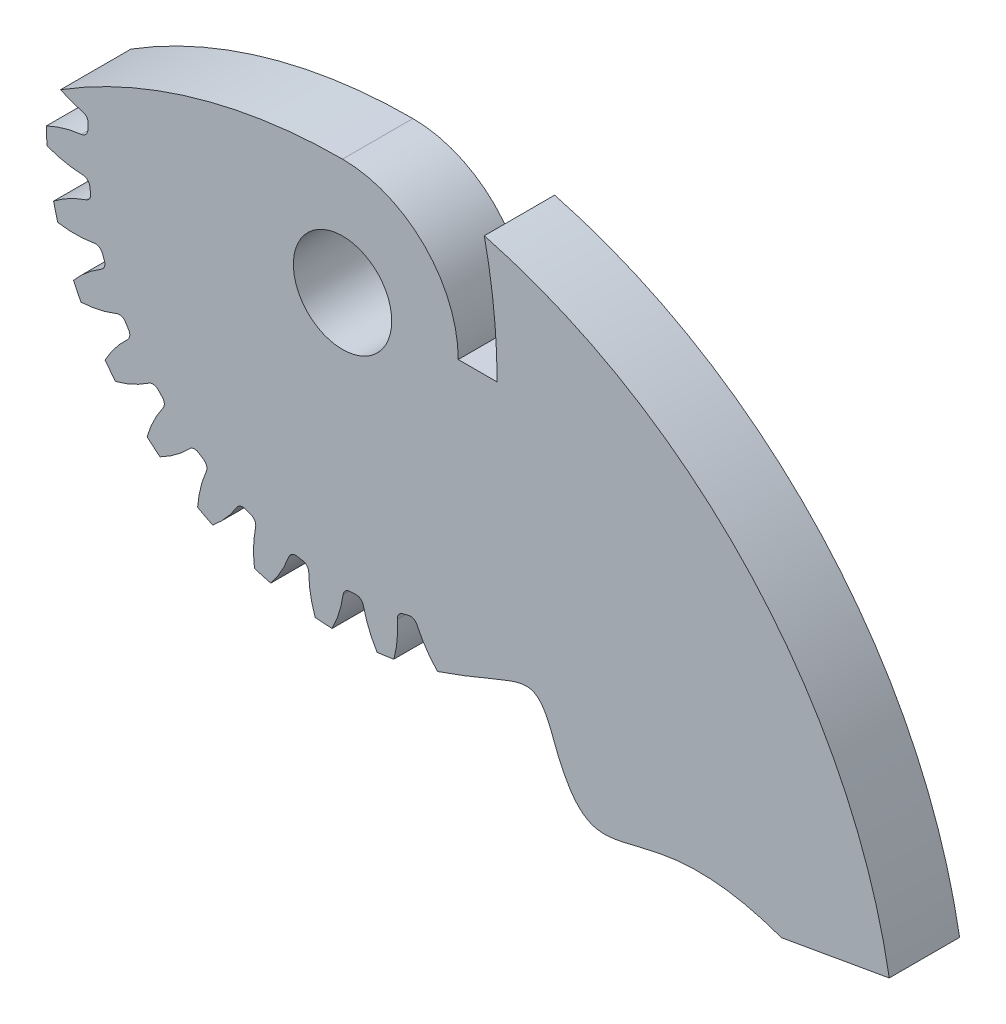
SolidWorks part; units mm, degrees
material "ABS"
ref_plane "Front" through (0, 0, 0) normal (0, 0, 1) x (1, 0, 0)
ref_plane "Top" through (0, 0, 0) normal (0, 1, 0) x (1, 0, 0)
ref_plane "Right" through (0, 0, 0) normal (1, 0, 0) x (0, 0, -1)
sketch "Sketch3" plane through (0, 0, 0) normal (0, 0, 1) x (1, 0, 0)
  circle A0 centre (0, 0) radius 40.64
  dimension "od" = 81.28
extrude "gearBody" add sketch "Sketch3" along normal blind 9.652
sketch "Sketch2" plane through (0, 0, 0) normal (0, 0, 1) x (1, 0, 0)
  line L0 (0, 0) -> (34.0786, 14.1158) construction
  line L1 (45.4751, -11.4855) -> (0, 0) construction
  line L2 (0, 0) -> (36.3143, 0) construction
  line L3 (38.0972, -0.458) -> (37.8451, -4.4001) construction
  line L5 (37.9712, -2.4291) -> (0, 0) construction
  line L7 (0, 0) -> (36.8864, 0) construction
  arc A0 (36.879, -0.7403) -> (36.6727, -3.9649) centre (0, 0) ccw construction
  arc A1 (40.637, 0.4947) -> (40.2427, -5.6687) centre (0, 0) ccw construction
  arc A2 (38.0972, -0.458) -> (37.8451, -4.4001) centre (0, 0) ccw construction
  arc A3 (34.9015, -2.6404) -> (34.9534, -1.8283) centre (0, 0) ccw
  arc A4 (45.4751, -11.4855) -> (35.6466, -3.6712) centre (32.0022, -18.3431) ccw
  arc A5 (45.4751, -11.4855) -> (46.5679, 5.5974) centre (0, 0) ccw
  arc A6 (46.5679, 5.5974) -> (35.8238, -0.9008) centre (34.0786, 14.1158) cw
  arc A7 (34.9534, -1.8283) -> (35.8238, -0.9008) centre (35.9376, -1.8798) cw
  arc A8 (35.6466, -3.6712) -> (34.9015, -2.6404) centre (35.8842, -2.7147) cw
  point P6 (46.5679, 5.5974)
  point P22 (45.4751, -11.4855)
  dimension "baseDia" = 73.7729
  dimension "od" = 81.28
  dimension "pd" = 76.2
  dimension "rd" = 70.0024
  dimension "rFillet" = 0.9855
  dimension "pointX" = 46.5679
  dimension "pointY" = 5.5974
  dimension "CTT" = 3.9421
  dimension "flankCenterAngle" = 22.5
extrude "toothCut" cut sketch "Sketch2" along normal through all
pattern_circular "CirPattern1" count 30 over 360 about axis through (0, 0, 9.652) along (0, 0, -1) of "toothCut"
sketch "hub1Dia" plane through (0, 0, 0) normal (0, 0, -1) x (-1, 0, 0)
  circle A0 centre (0, 0) radius 12.7
  dimension "hub1Dia" = 25.4
sketch "hub2Dia" plane through (0, 0, 9.652) normal (0, 0, 1) x (1, 0, 0)
  circle A0 centre (0, 0) radius 12.7
  dimension "hub2dia" = 25.4
sketch "boreDia" plane through (0, 0, 0) normal (0, 0, 1) x (1, 0, 0)
  circle A0 centre (0, 0) radius 6.7469
  dimension "boreDia" = 13.4937
extrude "bore" cut sketch "boreDia" against normal mid plane 25400
sketch "Sketch4" plane through (0, 0, 9.652) normal (0, 0, 1) x (1, 0, 0)
  circle A0 centre (0, -57.15) radius 76.1746
  arc A2 (-41.7195, 6.5842) -> (41.7195, 6.5842) centre (0, 0) cw
  dimension "D1" = 152.3492
  dimension "D2" = 57.15
extrude "Cut-Extrude1" cut sketch "Sketch4" against normal through all contours A0 region at (0, 26.0638, 9.652)
sketch "Sketch5" plane through (0, 0, 9.652) normal (0, 0, 1) x (1, 0, 0)
  line L0 (0, 19.0246) -> (21.5163, 3.7176)
  line L1 (21.5163, 3.7176) -> (8.9608, -26.928)
  line L2 (8.9608, -26.928) -> (13.028, -38.4952)
  line L3 (0, 0) -> (0, -57.15) construction
  line L4 (0, -57.15) -> (-54.1615, -3.586) construction
  line L5 (0, -57.15) -> (65.9691, -95.2373) construction
  line L9 (0, -57.15) -> (75.0173, -43.9224) construction
  line L12 (60.232, -46.5295) -> (75.0173, -43.9224)
  line L13 (0, -57.15) -> (29.696, -40.005) construction
  line L14 (29.696, -40.005) -> (26.521, -34.5057) construction
  circle A1 centre (0, -57.15) radius 76.1746 construction
  arc A5 (0, 19.0246) -> (75.0173, -43.9224) centre (0, -57.15) cw
  circle A6 centre (0, -57.15) radius 21.59 construction
  circle A12 centre (49.4934, -85.725) radius 40.64 construction
  spline S0 degree 3 poles (13.028, -38.4952) (20.557, -35.948) (26.6517, -31.726) (34.6651, -56.7545) (39.5345, -39.0169) (60.232, -46.5295) knots 0 0 0 0 0.118515 0.218515 1 1 1 1
  point P28 (21.569, -56.1981)
  dimension "D1" = 43.18
  dimension "D3" = 81.28
  dimension "D6" = 152.3492
  dimension "D2" = 120
  dimension "D4" = 57.15
  dimension "D8" = 57.15
  dimension "D7" = 60
  dimension "D9" = 34.29
  dimension "D10" = 6.35
  dimension "D5" = 80
extrude "Boss-Extrude1" add sketch "Sketch5" against normal up to surface (9.652 mm away) up to face at (6.7469, 0, 0)
sketch "Sketch6" plane through (0, 0, 9.652) normal (0, 0, 1) x (1, 0, 0)
  line L1 (-41.2993, 3.0747) -> (-42.3397, 6.1739)
  line L2 (15.875, 0) -> (21.209, 0)
  circle A0 centre (0, -57.15) radius 76.1746 construction
  arc A1 (75.0173, -43.9224) -> (-34.0662, 10.9827) centre (0, -57.15) ccw construction
  circle A2 centre (0, 0) radius 15.875 construction
  arc A3 (0, 15.875) -> (15.875, 0) centre (0, 0) cw
  arc A4 (19.4523, 16.499) -> (-42.3397, 6.1739) centre (0, -57.15) ccw
  arc A5 (0, 15.875) -> (-41.2993, 3.0747) centre (0, -57.15) ccw
  circle A6 centre (0, 0) radius 21.209 construction
  circle A8 centre (-57.15, 0) radius 78.359 construction
  arc A9 (21.209, 0) -> (19.4523, 16.499) centre (-57.15, 0) ccw
  dimension "D4" = 57.15
  dimension "D1" = 31.75
  dimension "D2" = 42.418
  dimension "D3" = 156.718
extrude "Cut-Extrude2" cut sketch "Sketch6" against normal through all
equation "\"Bodytube_OD\" = 6.17in"
equation "\"Bodytube_ID\" = 5.998in"
equation "\"Fwd_Tube_Length\" = 40in"
equation "\"Mid_Tube_Length\" = 1in"
equation "\"Aft_Section_Length\"= 39in"
equation "\"Mid_Coupler_Length\"= 13in"
equation "\"Aft_Lower_Length\"= 22in"
equation "\"AB_Coupler_OD_Length\"= 1in"
equation "\"AB_Coupling_Section_Length\"= 0.375in"
equation "\"AB_Coupler_Length\"= \"AB_Coupler_OD_Length\" + \"AB_Coupling_Section_Length\" * 2"
equation "\"Cutout_Angle\" = 80"
equation "\"AB_Paddle_Height\" = 0.375in"
equation "\"AB_Coupler_Num_Screws\"= 6"
equation "\"Num_Cutouts\" = 3"
equation "\"AB_Coupler_OD\"= 6.17in"
equation "\"AB_Coupler_ID\"= 5.75in"
equation "\"AB_Coupler_Surface_Diameter\"= 5.998in"
equation "\"AB_Coupling_Screw_Diameter\"= 0.1065in"
equation "\"AB_Central_Bushing_Length\" = .75in"
equation "\"Lead_Screw_Dist\" = 3.4in"
equation "\"Lead_Screw_Diam\" = 0.386in"
equation "\"Lead_Screw_Length\" = (\"Mid_Coupler_Length\" + 2*0.375in + 2*0.5in)"
equation "\"Paddle_Pin_Offset\" = .25in"
equation "\"Paddle_Pin_Radius\" = 2.25in"
equation "\"Fwd_BKHD_From_Top\" = 18in"
equation "\"D1@Sketch4\"=\"Bodytube_ID\""
equation "\"D2@Sketch4\"=\"Paddle_Pin_Radius\""
equation "\"D3@Sketch5\"=\"Paddle_Gear_OD\""
equation "\"D4@Sketch5\"=\"Paddle_Pin_Radius\""
equation "\"Motor_OD\" = 4in"
equation "\"Aft_Upper_Length\"= \"Aft_Section_Length\" - \"Aft_Lower_Length\" - \"AB_Coupler_OD_Length\""
equation "\"Paddle_Gear_OD\" = 3.2in"
equation "\"D5@Sketch5\"=\"Cutout_Angle\""
equation "\"D6@Sketch5\"=\"Bodytube_ID\""
equation "\"D1@Sketch6\"=\"AB_Coupler_ID\"-2*\"Paddle_Pin_Radius\""
equation "\"D2@Sketch6\"=\"Bodytube_OD\"-2*\"Paddle_Pin_Radius\""
equation "\"D3@Sketch6\"=\"Bodytube_OD\""
equation "\"D4@Sketch6\"=\"Paddle_Pin_Radius\""
equation "\"D8@Sketch5\"=\"Paddle_Pin_Radius\""
equation "\"Drive_Gear_OD\" = 1.7in"
equation "\"Fin_Thickness\"= .118in"
equation "\"Guiderail_Cutout_Diameter\"= 1.5in"
equation "\"DB9_Hole_Dist\" = 25mm"
equation "\"D1@Sketch5\"=\"Drive_Gear_OD\""
